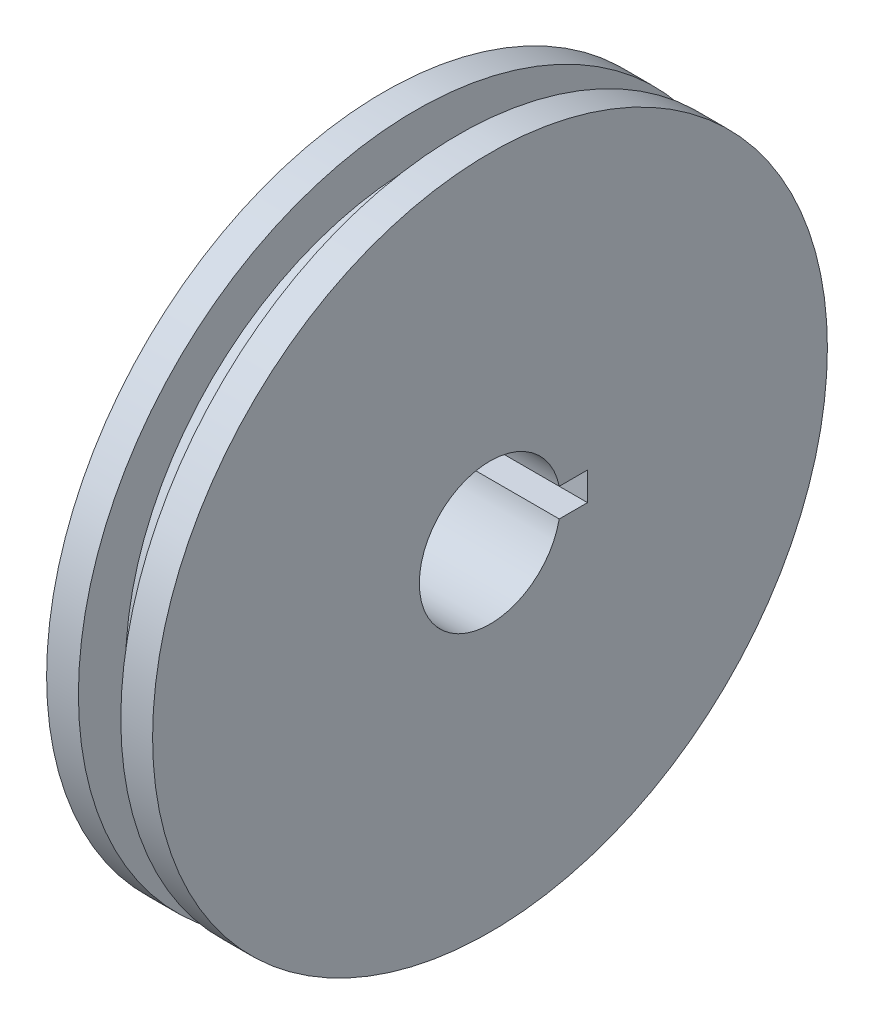
SolidWorks part; units mm, degrees
ref_plane "前视基准面" through (0, 0, 0) normal (0, 0, 1) x (1, 0, 0)
ref_plane "上视基准面" through (0, 0, 0) normal (0, 1, 0) x (1, 0, 0)
ref_plane "右视基准面" through (0, 0, 0) normal (1, 0, 0) x (0, 0, -1)
sketch "草图1" plane through (0, 0, 0) normal (0, 1, 0) x (1, 0, 0)
  line L0 (-58.3273, 0) -> (70.5845, 0) construction
  line L1 (0, 43.4285) -> (0, -42.7945) construction
  line L2 (-7.5, 10) -> (-7.5, 47.75)
  line L3 (-7.5, 47.75) -> (-3, 47.75)
  line L4 (7.5, 10) -> (7.5, 47.75)
  line L5 (-3, 47.75) -> (-3, 41.079)
  line L6 (-3, 41.079) -> (3, 41.079)
  line L7 (3, 47.75) -> (3, 41.079)
  line L8 (3, 47.75) -> (7.5, 47.75)
  line L10 (-7.5, 10) -> (7.5, 10)
  point P10 (0, 47.75)
  point P14 (0, 41.079)
  dimension "D3" = 6
  dimension "D1" = 15
  dimension "D2" = 47.75
revolve "旋转1" add sketch "草图1" angle 360 about L0
sketch "草图2" plane through (7.5, 0, 0) normal (1, 0, 0) x (0, 0, -1)
  line L0 (-20.5551, 0) -> (27.2636, 0) construction
  line L1 (9.798, 2) -> (13.798, 2)
  line L2 (13.798, 2) -> (13.798, -2)
  line L3 (9.798, -2) -> (13.798, -2)
  circle A0 centre (0, 0) radius 10 construction
  arc A1 (9.798, -2) -> (9.798, 2) centre (0, 0) ccw
  point P10 (13.798, 0)
  dimension "D1" = 4
  dimension "D2" = 4
extrude "切除-拉伸1" cut sketch "草图2" against normal blind 15
